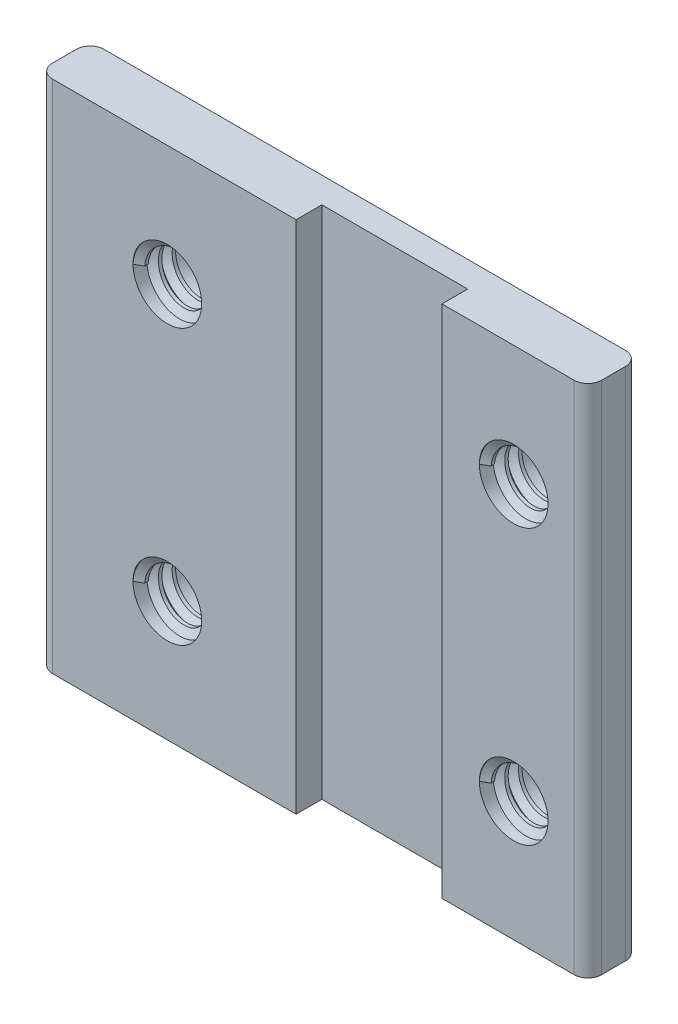
SolidWorks part; units mm, degrees
ref_plane "Front Plane" through (0, 0, 0) normal (0, 0, 1) x (1, 0, 0)
ref_plane "Top Plane" through (0, 0, 0) normal (0, 1, 0) x (1, 0, 0)
ref_plane "Right Plane" through (0, 0, 0) normal (1, 0, 0) x (0, 0, -1)
sketch "Sketch1" plane through (0, 0, 0) normal (0, 0, 1) x (1, 0, 0)
  line L0 (0, 0) -> (0, 47.625)
  line L1 (0, 47.625) -> (-50.8, 47.625)
  line L2 (-50.8, 47.625) -> (-50.8, 0)
  line L3 (-50.8, 0) -> (0, 0)
  line L4 (0, 23.8125) -> (-50.8, 23.8125) construction
  line L6 (-13.4937, 47.625) -> (-26.9875, 47.625)
  line L7 (-13.4937, 47.625) -> (-13.4937, 0)
  line L8 (-13.4937, 0) -> (-26.9875, 0)
  line L9 (-26.9875, 47.625) -> (-26.9875, 0)
  circle A0 centre (-6.858, 36.5125) radius 3.175
  circle A1 centre (-6.858, 11.1125) radius 3.175
  dimension "D3" = 6.35
  dimension "D1" = 47.625
  dimension "D2" = 50.8
  dimension "D4" = 6.858
  dimension "D5" = 12.7
  dimension "D6" = 13.4937
  dimension "D7" = 13.4937
extrude "Boss-Extrude2" add sketch "Sketch1" along normal blind 2.3813 contours L7 L4 L9 L3 | L4 L7 L1 L9 region at (-20.2406, 11.9062, 0) region at (-20.2406, 35.7187, 0)
extrude "Boss-Extrude3" add sketch "Sketch1<3>" along normal blind 4.7625 contours L4 L9 L1 L2 | L9 L4 L2 L3 | L4 L0 L1 L7 A0 | L0 L4 L7 L3 A1 region at (-6.7469, 0.2737, 0) region at (-6.7469, 24.0862, 0) region at (-38.8937, 11.9062, 0) region at (-38.8937, 35.7187, 0)
sketch "Sketch1<3>" plane through (0, 0, 0) normal (0, 0, 1) x (1, 0, 0) same geometry as "Sketch1"
thread "Thread1" pitch 1.27 method extrude profile "Thread Profile1" start angle 0, offset 0, length 0, pitch 1.27, diameter 6.35
ref_plane "Plane1" through (-10.033, 36.5125, 4.7625) normal (0, -1, 0) x (-1, 0, 0)
sketch "Thread Profile1" plane through (-10.033, 36.5125, 4.7625) normal (0, -1, 0) x (-1, 0, 0)
  line L0 (0, 0) -> (0, 1.27) construction
  line L11 (0, 0) -> (0, 1.1112)
  line L12 (0, 1.1112) -> (-0.6874, 0.7144)
  line L13 (-0.6874, 0.7144) -> (-0.6874, 0.3969)
  line L15 (-0.6874, 0.3969) -> (0, 0)
  line L17 (-0.6874, 0.5556) -> (0, 0.5556) construction
  point P2 (0, 0)
  dimension "Pitch" = 1.27
  dimension "Profile_Angle" = 60
  dimension "Profile_Land" = 0.3175
  dimension "Profile_Height" = 0.6874
thread "Thread2" pitch 1.27 method extrude profile "Thread Profile2" start angle 0, offset 0, length 0, pitch 1.27, diameter 6.35
ref_plane "Plane2" through (-10.033, 11.1125, 4.7625) normal (0, -1, 0) x (-1, 0, 0)
sketch "Thread Profile2" plane through (-10.033, 11.1125, 4.7625) normal (0, -1, 0) x (-1, 0, 0)
  line L0 (0, 0) -> (0, 1.27) construction
  line L11 (0, 0) -> (0, 1.1112)
  line L12 (0, 1.1112) -> (-0.6874, 0.7144)
  line L13 (-0.6874, 0.7144) -> (-0.6874, 0.3969)
  line L15 (-0.6874, 0.3969) -> (0, 0)
  line L17 (-0.6874, 0.5556) -> (0, 0.5556) construction
  point P2 (0, 0)
  dimension "Pitch" = 1.27
  dimension "Profile_Angle" = 60
  dimension "Profile_Land" = 0.3175
  dimension "Profile_Height" = 0.6874
sketch "Sketch2" plane through (0, 0, 4.7625) normal (0, 0, 1) x (1, 0, 0)
  line L0 (-50.8, 23.8125) -> (-26.9875, 23.8125) construction
  line L1 (-50.8, 47.625) -> (-50.8, 0) construction
  line L2 (-26.9875, 47.625) -> (-26.9875, 0) construction
  circle A0 centre (-38.8938, 36.5125) radius 3.175
  circle A1 centre (-38.8938, 11.1125) radius 3.175
  point P6 (-38.8937, 23.8125)
  dimension "D1" = 6.35
  dimension "D2" = 12.7
extrude "Cut-Extrude1" cut sketch "Sketch2" against normal up to next
thread "Thread3" pitch 1.27 method extrude profile "Thread Profile3" start angle 0, offset 0, length 0, pitch 1.27, diameter 6.35
ref_plane "Plane4" through (-42.0688, 36.5125, 4.7625) normal (0, -1, 0) x (-1, 0, 0)
sketch "Thread Profile3" plane through (-42.0688, 36.5125, 4.7625) normal (0, -1, 0) x (-1, 0, 0)
  line L0 (0, 0) -> (0, 1.27) construction
  line L11 (0, 0) -> (0, 1.1112)
  line L12 (0, 1.1112) -> (-0.6874, 0.7144)
  line L13 (-0.6874, 0.7144) -> (-0.6874, 0.3969)
  line L15 (-0.6874, 0.3969) -> (0, 0)
  line L17 (-0.6874, 0.5556) -> (0, 0.5556) construction
  point P2 (0, 0)
  dimension "Pitch" = 1.27
  dimension "Profile_Angle" = 60
  dimension "Profile_Land" = 0.3175
  dimension "Profile_Height" = 0.6874
thread "Thread4" pitch 1.27 method extrude profile "Thread Profile4" start angle 0, offset 0, length 0, pitch 1.27, diameter 6.35
ref_plane "Plane5" through (-42.0688, 11.1125, 4.7625) normal (0, -1, 0) x (-1, 0, 0)
sketch "Thread Profile4" plane through (-42.0688, 11.1125, 4.7625) normal (0, -1, 0) x (-1, 0, 0)
  line L0 (0, 0) -> (0, 1.27) construction
  line L11 (0, 0) -> (0, 1.1112)
  line L12 (0, 1.1112) -> (-0.6874, 0.7144)
  line L13 (-0.6874, 0.7144) -> (-0.6874, 0.3969)
  line L15 (-0.6874, 0.3969) -> (0, 0)
  line L17 (-0.6874, 0.5556) -> (0, 0.5556) construction
  point P2 (0, 0)
  dimension "Pitch" = 1.27
  dimension "Profile_Angle" = 60
  dimension "Profile_Land" = 0.3175
  dimension "Profile_Height" = 0.6874
fillet "Fillet1" radius 1.27 4 edges at (0, 23.8125, 0) (0, 23.8125, 4.7625) (-50.8, 23.8125, 0) (-50.8, 23.8125, 4.7625)
